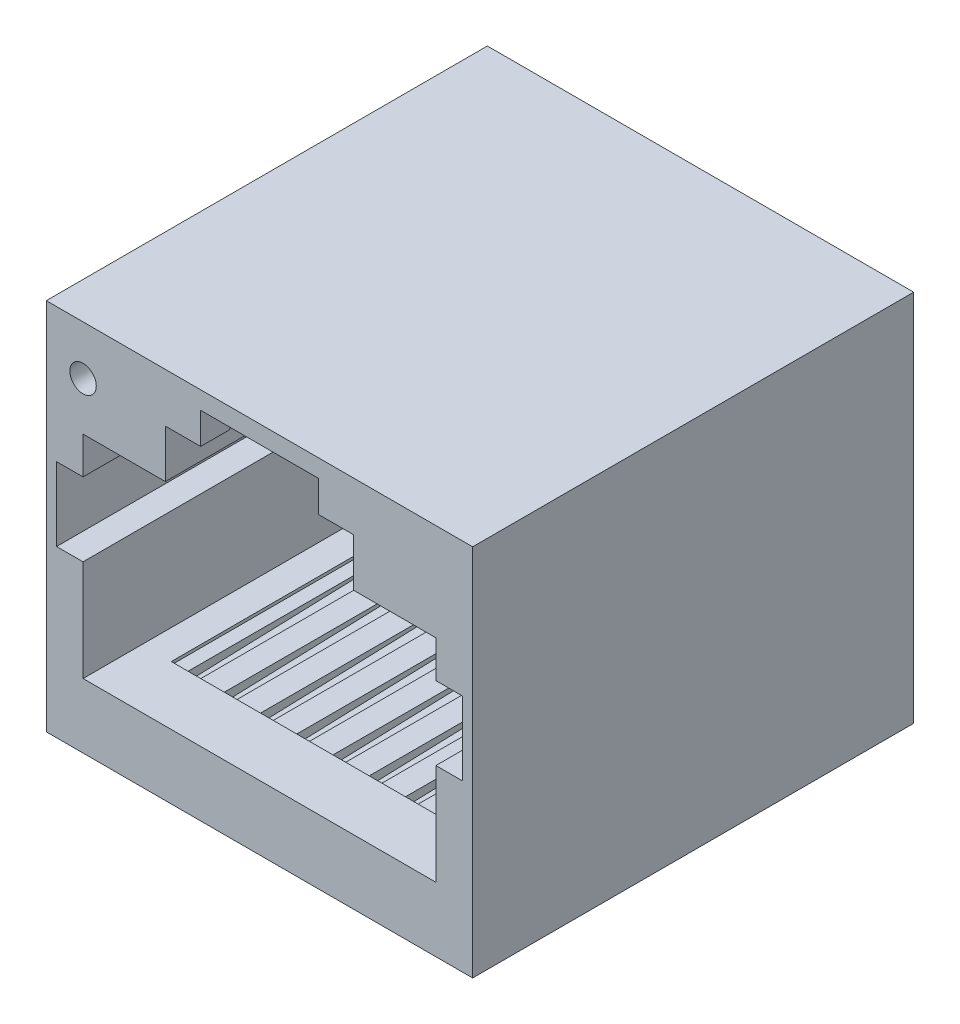
SolidWorks part; units mm, degrees
material "Custom Plastic"
ref_plane "Front Plane" through (0, 0, 0) normal (0, 0, 1) x (1, 0, 0)
ref_plane "Top Plane" through (0, 0, 0) normal (0, 1, 0) x (1, 0, 0)
ref_plane "Right Plane" through (0, 0, 0) normal (1, 0, 0) x (0, 0, -1)
sketch "Sketch2" plane through (0, 0, 0) normal (0, 1, 0) x (1, 0, 0)
  line L1 (-7.25, -7.5) -> (7.25, -7.5)
  line L2 (-7.25, -7.5) -> (-7.25, 7.5)
  line L3 (-7.25, 7.5) -> (7.25, 7.5)
  line L4 (7.25, -7.5) -> (7.25, 7.5)
  line L5 (-7.25, -7.5) -> (7.25, 7.5) construction
  line L6 (-7.25, 7.5) -> (7.25, -7.5) construction
  point P0 (0, 0)
  dimension "D1" = 14.5
  dimension "D2" = 15
extrude "Outline extrusion" add sketch "Sketch2" along normal blind 12.7
sketch "Sketch3" plane through (0, 0, 7.5) normal (0, 0, 1) x (1, 0, 0)
  line L0 (-7.25, 12.7) -> (7.25, 12.7) construction
  line L1 (-6, 9.3952) -> (6, 9.3952)
  line L2 (-6, 9.3952) -> (-6, 2.1952)
  line L3 (-6, 2.1952) -> (6, 2.1952)
  line L4 (6, 9.3952) -> (6, 2.1952)
  line L5 (-3.2, 9.3952) -> (3.2, 9.3952)
  line L6 (-3.2, 9.3952) -> (-3.2, 11.0305)
  line L7 (-3.2, 11.0305) -> (3.2, 11.0305)
  line L8 (3.2, 9.3952) -> (3.2, 11.0305)
  line L9 (-2, 11.0305) -> (2, 11.0305)
  line L10 (-2, 11.0305) -> (-2, 12.0952)
  line L11 (-2, 12.0952) -> (2, 12.0952)
  line L12 (2, 11.0305) -> (2, 12.0952)
  line L13 (-6, 8.1332) -> (-6.9, 8.1332)
  line L14 (-6, 8.1332) -> (-6, 5.6332)
  line L15 (-6, 5.6332) -> (-6.9, 5.6332)
  line L16 (-6.9, 8.1332) -> (-6.9, 5.6332)
  line L17 (6, 8.1332) -> (6.9, 8.1332)
  line L18 (6, 8.1332) -> (6, 5.6332)
  line L19 (6, 5.6332) -> (6.9, 5.6332)
  line L20 (6.9, 8.1332) -> (6.9, 5.6332)
  point P22 (0, 12.7)
  point P23 (0, 12.0952)
  point P24 (0, 11.0305)
  point P25 (0, 9.3952)
  dimension "D1" = 0
  dimension "D2" = 0
  dimension "D3" = 0
  dimension "D4" = 12
  dimension "D5" = 7.2
  dimension "D6" = 2.5
  dimension "D7" = 2.5
  dimension "D8" = 0.9
  dimension "D9" = 0.9
  dimension "D10" = 4
  dimension "D11" = 6.4
  dimension "D12" = 9.9
  dimension "D13" = 0.6048
extrude "Cut-Extrude1" cut sketch "Sketch3" against normal blind 14 contours L4 L1 L2 L3 | L1 L8 L7 L6 | L7 L12 L11 L10 | L20 L17 L4 L19 | L16 L15 L14 L13 region at (0, 5.7952, 7.5) region at (0, 10.2129, 7.5) region at (0, 11.5629, 7.5) region at (6.45, 6.8832, 7.5)
sketch "Sketch5" plane through (0, 0, 7.5) normal (0, 0, 1) x (1, 0, 0)
  circle A0 centre (-6, 11.0305) radius 0.45
  dimension "D2" = 0.9
  dimension "D1" = 0
extrude "Cut-Extrude2" cut sketch "Sketch5" against normal blind 14
sketch "Sketch6" plane through (0, 0, -6.5) normal (0, 0, 1) x (1, 0, 0)
  line L0 (-2, 11.9952) -> (2, 11.9952)
  line L1 (-2, 11.0305) -> (-2, 12.0952) construction
  line L2 (2, 11.0305) -> (2, 12.0952) construction
  line L3 (-2, 12.0952) -> (2, 12.0952) construction
  line M6 (2, 11.0305) -> (2, 12.0952)
  line M7 (2, 12.0952) -> (-2, 12.0952)
  line M8 (-2, 12.0952) -> (-2, 11.0305)
  dimension "D1" = 0.1
extrude "Boss-Extrude1" add sketch "Sketch6" along normal blind 11.5 contours L0 M8 M6 M7 region at (0, 12.0452, -6.5)
sketch "Sketch7" plane through (0, 0, -6.5) normal (0, 0, 1) x (1, 0, 0)
  line L1 (-3.2, 11.0305) -> (-2, 11.0305)
  line L2 (-3.2, 11.0305) -> (-3.2, 11.9952)
  line L3 (-3.2, 11.9952) -> (-2, 11.9952)
  line L4 (-2, 11.0305) -> (-2, 11.9952)
  line L5 (3.2, 11.0305) -> (2, 11.0305)
  line L6 (3.2, 11.0305) -> (3.2, 11.9952)
  line L7 (3.2, 11.9952) -> (2, 11.9952)
  line L8 (2, 11.0305) -> (2, 11.9952)
extrude "Cut-Extrude3" cut sketch "Sketch7" along normal blind 13
sketch "Sketch8" plane through (0, 0, -6.5) normal (0, 0, 1) x (1, 0, 0)
  line L0 (3.2, 10.6952) -> (-3.2, 10.6952)
  line L1 (3.2, 9.3952) -> (3.2, 11.9952) construction
  line L2 (-3.2, 9.3952) -> (-3.2, 11.9952) construction
  line L19 (3.2, 9.3952) -> (3.2, 11.9952)
  line L20 (3.2, 11.9952) -> (-3.2, 11.9952)
  line L21 (-3.2, 11.9952) -> (-3.2, 9.3952)
  line L22 (-3.2, 9.3952) -> (-6, 9.3952)
  line L23 (-6, 9.3952) -> (-6, 8.1332)
  line L24 (-6, 8.1332) -> (-6.9, 8.1332)
  line L25 (-6.9, 8.1332) -> (-6.9, 5.6332)
  line L26 (-6.9, 5.6332) -> (-6, 5.6332)
  line L27 (-6, 5.6332) -> (-6, 2.1952)
  line L28 (-6, 2.1952) -> (6, 2.1952)
  line L29 (6, 2.1952) -> (6, 5.6332)
  line L30 (6, 5.6332) -> (6.9, 5.6332)
  line L31 (6.9, 5.6332) -> (6.9, 8.1332)
  line L32 (6.9, 8.1332) -> (6, 8.1332)
  line L33 (6, 8.1332) -> (6, 9.3952)
  line L34 (6, 9.3952) -> (3.2, 9.3952)
  line L35 (3.2, 10.6952) -> (3.2, 11.9952)
  line L36 (3.2, 11.9952) -> (-3.2, 11.9952)
  line L37 (-3.2, 11.9952) -> (-3.2, 10.6952)
  line M17 (3.2, 9.3952) -> (3.2, 11.9952)
  line M19 (-3.2, 11.9952) -> (-3.2, 9.3952)
  line M20 (-3.2, 9.3952) -> (-6, 9.3952)
  line M21 (-6, 9.3952) -> (-6, 8.1332)
  line M22 (-6, 8.1332) -> (-6.9, 8.1332)
  line M23 (-6.9, 8.1332) -> (-6.9, 5.6332)
  line M24 (-6.9, 5.6332) -> (-6, 5.6332)
  line M25 (-6, 5.6332) -> (-6, 2.1952)
  line M26 (-6, 2.1952) -> (6, 2.1952)
  line M27 (6, 2.1952) -> (6, 5.6332)
  line M28 (6, 5.6332) -> (6.9, 5.6332)
  line M29 (6.9, 5.6332) -> (6.9, 8.1332)
  line M30 (6.9, 8.1332) -> (6, 8.1332)
  line M31 (6, 8.1332) -> (6, 9.3952)
  line M32 (6, 9.3952) -> (3.2, 9.3952)
  dimension "D1" = 0
extrude "Boss-Extrude2" add sketch "Sketch8" along normal blind 2 contours L0 M17 M19 M20 M21 M22 M23 M24 M25 M26 M27 M28 M29 M30 M31 M32 region at (0, 6.2009, -6.5)
sketch "Sketch9" plane through (0, 0, -4.5) normal (0, 0, 1) x (1, 0, 0)
  line L0 (-6, 8.7642) -> (-3.2, 8.7642)
  line L1 (-6, 9.3952) -> (-6, 8.1332) construction
  line L2 (-3.2, 9.3952) -> (-3.2, 8.7642)
  line L3 (3.2, 9.3952) -> (3.2, 8.7642)
  line L4 (3.2, 8.7642) -> (6, 8.7642)
  line L5 (6, 8.1332) -> (6, 9.3952) construction
  line L7 (-5.4, 8.1332) -> (-6.9, 8.1332)
  line L8 (-5.4, 8.1332) -> (-5.4, 5.6332)
  line L9 (-5.4, 5.6332) -> (-6.9, 5.6332)
  line L10 (-6.9, 8.1332) -> (-6.9, 5.6332)
  line L11 (5.4, 8.1332) -> (6.9, 8.1332)
  line L12 (5.4, 8.1332) -> (5.4, 5.6332)
  line L13 (5.4, 5.6332) -> (6.9, 5.6332)
  line L14 (6.9, 8.1332) -> (6.9, 5.6332)
  line M12 (-6, 8.1332) -> (-6.9, 8.1332)
  line M13 (-6.9, 8.1332) -> (-6.9, 5.6332)
  line M14 (-6.9, 5.6332) -> (-6, 5.6332)
  line M18 (6, 5.6332) -> (6.9, 5.6332)
  line M19 (6.9, 5.6332) -> (6.9, 8.1332)
  line M20 (6.9, 8.1332) -> (6, 8.1332)
  dimension "D1" = 1.5
  dimension "D2" = 1.5
  dimension "D3" = 2.5
  dimension "D4" = 2.5
extrude "Cut-Extrude4" cut sketch "Sketch9" against normal blind 1.5 contours L12 L13 L11 M18 M19 M20 | L9 L8 L7 M12 M13 M14 region at (-6.15, 6.8832, -4.5) region at (6.15, 6.8832, -4.5)
sketch "Sketch10" plane through (0, 0, -4.5) normal (0, 0, 1) x (1, 0, 0)
  line L0 (0, 11.4918) -> (0, 1.358) construction
  line L2 (-6, 2.1952) -> (6, 2.1952) construction
  line L3 (-4.0064, 2.1952) -> (-3.7048, 2.1952)
  line L4 (-4.0064, 2.1952) -> (-4.0064, 4.4645)
  line L5 (-4.0064, 4.4645) -> (-3.7048, 4.4645)
  line L6 (-3.7048, 2.1952) -> (-3.7048, 4.4645)
  line L7 (-6, 2.1952) -> (6, 2.1952) construction
  line L8 (-2.9048, 4.4645) -> (-2.6032, 4.4645)
  line L9 (-2.9048, 4.4645) -> (-2.9048, 2.1952)
  line L10 (-2.9048, 2.1952) -> (-2.6032, 2.1952)
  line L11 (-2.6032, 4.4645) -> (-2.6032, 2.1952)
  line L12 (0.4, 4.4645) -> (0.4, 2.1952)
  line L13 (-1.8032, 4.4645) -> (-1.5016, 4.4645)
  line L14 (-1.8032, 4.4645) -> (-1.8032, 2.1952)
  line L15 (-1.8032, 2.1952) -> (-1.5016, 2.1952)
  line L16 (-1.5016, 4.4645) -> (-1.5016, 2.1952)
  line L17 (-0.7016, 4.4645) -> (-0.4, 4.4645)
  line L18 (-0.7016, 4.4645) -> (-0.7016, 2.1952)
  line L19 (-0.7016, 2.1952) -> (-0.4, 2.1952)
  line L20 (-0.4, 4.4645) -> (-0.4, 2.1952)
  line L21 (0.7016, 2.1952) -> (0.4, 2.1952)
  line L22 (0.7016, 4.4645) -> (0.7016, 2.1952)
  line L23 (0.7016, 4.4645) -> (0.4, 4.4645)
  line L24 (1.5016, 4.4645) -> (1.5016, 2.1952)
  line L25 (1.8032, 2.1952) -> (1.5016, 2.1952)
  line L26 (1.8032, 4.4645) -> (1.8032, 2.1952)
  line L27 (1.8032, 4.4645) -> (1.5016, 4.4645)
  line L28 (2.6032, 4.4645) -> (2.6032, 2.1952)
  line L29 (2.9048, 2.1952) -> (2.6032, 2.1952)
  line L30 (2.9048, 4.4645) -> (2.9048, 2.1952)
  line L31 (2.9048, 4.4645) -> (2.6032, 4.4645)
  line L32 (3.7048, 2.1952) -> (3.7048, 4.4645)
  line L33 (4.0064, 4.4645) -> (3.7048, 4.4645)
  line L34 (4.0064, 2.1952) -> (4.0064, 4.4645)
  line L35 (4.0064, 2.1952) -> (3.7048, 2.1952)
  point P23 (-1.6524, 4.4645)
  dimension "D1" = 0.8
  dimension "D2" = 0.8
  dimension "D3" = 0.8
  dimension "D4" = 0.4
extrude "Cut-Extrude5" cut sketch "Sketch10" against normal blind 1.5
sketch "Sketch12" plane through (0, 2.1952, 0) normal (0, 1, 0) x (1, 0, 0)
  line L0 (-6, 4.5) -> (-4.0064, 4.5) construction
  line L1 (-5, 4.5) -> (5, 4.5)
  line L2 (-5, 4.5) -> (-5, -5.5)
  line L3 (-5, -5.5) -> (5, -5.5)
  line L4 (5, 4.5) -> (5, -5.5)
  line L6 (6, 4.5) -> (6, -7.5) construction
  line L7 (-6, -7.5) -> (6, -7.5) construction
  line L8 (-6, 4.5) -> (-6, -7.5) construction
  dimension "D1" = 0
  dimension "D2" = 1
  dimension "D3" = 2
  dimension "D4" = 1
extrude "Cut-Extrude6" cut sketch "Sketch12" against normal blind 0.1
sketch "Sketch13" plane through (0, 2.0952, 0) normal (0, 1, 0) x (1, 0, 0)
  line L0 (0, 5.67) -> (0, -6.4349) construction
  line L1 (-5, -5.5) -> (5, -5.5) construction
  line L2 (-4.5293, 3.5) -> (-4.097, 3.5)
  line L3 (-4.5293, 3.5) -> (-4.5293, -5.5)
  line L4 (-4.5293, -5.5) -> (-4.097, -5.5)
  line L5 (-4.097, 3.5) -> (-4.097, -5.5)
  line L6 (-3.297, -5.5) -> (-2.8646, -5.5)
  line L7 (-3.297, -5.5) -> (-3.297, 3.5)
  line L8 (-3.297, 3.5) -> (-2.8646, 3.5)
  line L9 (-2.8646, -5.5) -> (-2.8646, 3.5)
  line L10 (-2.0646, 3.5) -> (-1.6323, 3.5)
  line L11 (-2.0646, 3.5) -> (-2.0646, -5.5)
  line L12 (-2.0646, -5.5) -> (-1.6323, -5.5)
  line L13 (-1.6323, 3.5) -> (-1.6323, -5.5)
  line L14 (-0.8323, -5.5) -> (-0.4, -5.5)
  line L15 (-0.8323, -5.5) -> (-0.8323, 3.5)
  line L16 (-0.8323, 3.5) -> (-0.4, 3.5)
  line L17 (-0.4, -5.5) -> (-0.4, 3.5)
  line L18 (0.4, -5.5) -> (0.4, 3.5)
  line L19 (0.8323, 3.5) -> (0.4, 3.5)
  line L20 (0.8323, -5.5) -> (0.8323, 3.5)
  line L21 (0.8323, -5.5) -> (0.4, -5.5)
  line L22 (1.6323, 3.5) -> (1.6323, -5.5)
  line L23 (2.0646, -5.5) -> (1.6323, -5.5)
  line L24 (2.0646, 3.5) -> (2.0646, -5.5)
  line L25 (2.0646, 3.5) -> (1.6323, 3.5)
  line L26 (2.8646, -5.5) -> (2.8646, 3.5)
  line L27 (3.297, 3.5) -> (2.8646, 3.5)
  line L28 (3.297, -5.5) -> (3.297, 3.5)
  line L29 (3.297, -5.5) -> (2.8646, -5.5)
  line L30 (4.097, 3.5) -> (4.097, -5.5)
  line L31 (4.5293, -5.5) -> (4.097, -5.5)
  line L32 (4.5293, 3.5) -> (4.5293, -5.5)
  line L33 (4.5293, 3.5) -> (4.097, 3.5)
  dimension "D1" = 0.8
  dimension "D2" = 0.8
  dimension "D3" = 0.8
  dimension "D4" = 0.4
  dimension "D5" = 0
  dimension "D6" = 9
  dimension "D7" = 0
  dimension "D8" = 0
  dimension "D9" = 0
extrude "Cut-Extrude7" cut sketch "Sketch13" against normal blind 0.3
sketch "Sketch14" plane through (-4.5293, 0, 0) normal (1, 0, 0) x (0, 0, -1)
  line L0 (3.5, 2.0952) -> (-5.5, 1.7952)
  line L1 (3.5, 1.7952) -> (-5.5, 1.7952) construction
  line L2 (3.5, 1.7952) -> (-5.5, 1.7952) construction
  line L3 (-5.5, 1.7952) -> (3.5, 1.7952)
  line L4 (3.5, 1.7952) -> (3.5, 2.0952)
extrude "Boss-Extrude5" add sketch "Sketch14" along normal blind 10
